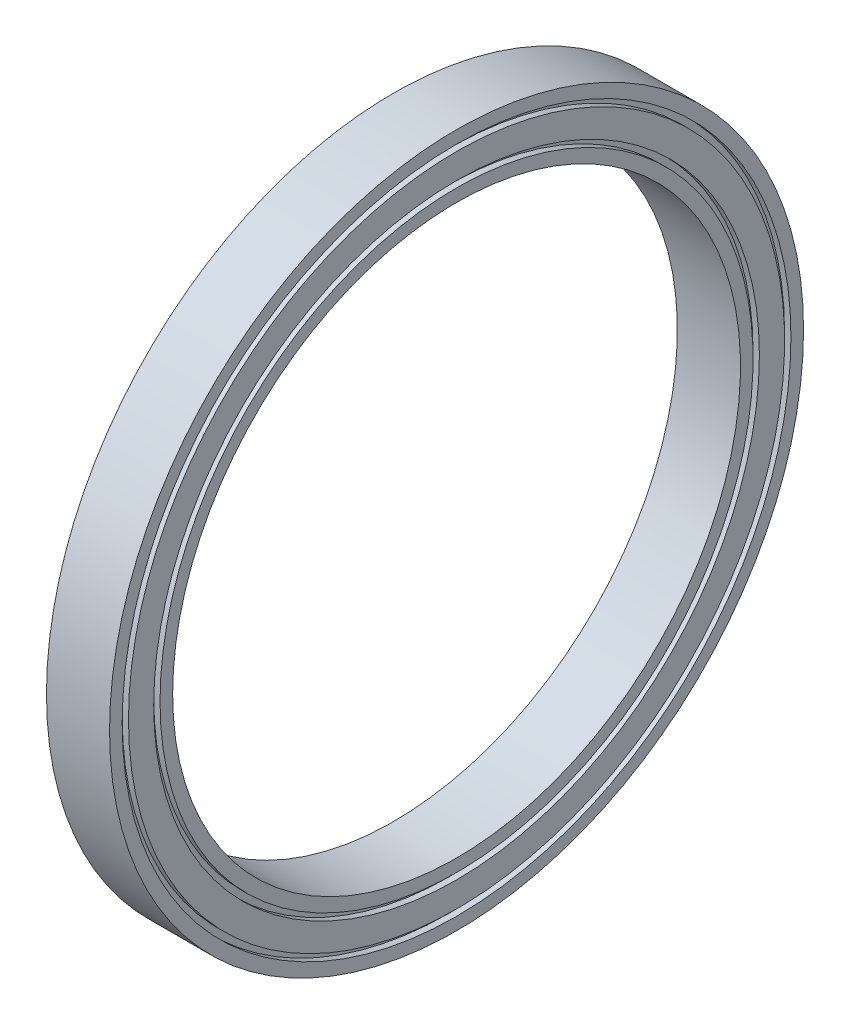
SolidWorks part; units mm, degrees
ref_plane "Front Plane" through (0, 0, 0) normal (0, 0, 1) x (1, 0, 0)
ref_plane "Top Plane" through (0, 0, 0) normal (0, 1, 0) x (1, 0, 0)
ref_plane "Right Plane" through (0, 0, 0) normal (1, 0, 0) x (0, 0, -1)
sketch "Sketch1" plane through (0, 0, 0) normal (0, 0, 1) x (1, 0, 0)
  line L0 (0, 0) -> (0, 22.5) construction
  line L1 (0, 22.5) -> (0, 27.5) construction
  line L2 (-2.5, 27.5) -> (2.5, 27.5)
  line L3 (2.5, 27.5) -> (2.5, 26.5)
  line L4 (2.5, 26.5) -> (2, 26.5)
  line L5 (2, 26.5) -> (2, 26)
  line L6 (2, 26) -> (2.5, 26)
  line L7 (2.5, 26) -> (2.5, 24)
  line L8 (2.5, 25) -> (0, 25) construction
  line L9 (2, 24) -> (2.5, 24)
  line L10 (2, 23.5) -> (2, 24)
  line L11 (2.5, 23.5) -> (2, 23.5)
  line L12 (2.5, 22.5) -> (2.5, 23.5)
  line L13 (-2.5, 22.5) -> (2.5, 22.5)
  line L14 (-2.5, 22.5) -> (-2.5, 23.5)
  line L15 (-2.5, 23.5) -> (-2, 23.5)
  line L16 (-2, 23.5) -> (-2, 24)
  line L17 (-2, 24) -> (-2.5, 24)
  line L18 (-2.5, 26) -> (-2.5, 24)
  line L19 (-2, 26) -> (-2.5, 26)
  line L20 (-2, 26.5) -> (-2, 26)
  line L21 (-2.5, 26.5) -> (-2, 26.5)
  line L22 (-2.5, 27.5) -> (-2.5, 26.5)
  line L23 (0, 0) -> (13.2088, 0) construction
  point P26 (-2, 24.2949)
  dimension "D1" = 2.5
  dimension "D2" = 2
  dimension "D3" = 0.5
  dimension "D4" = 5
  dimension "D5" = 1
  dimension "D6" = 27.5
revolve "Revolve1" add sketch "Sketch1" angle 360 about L23
